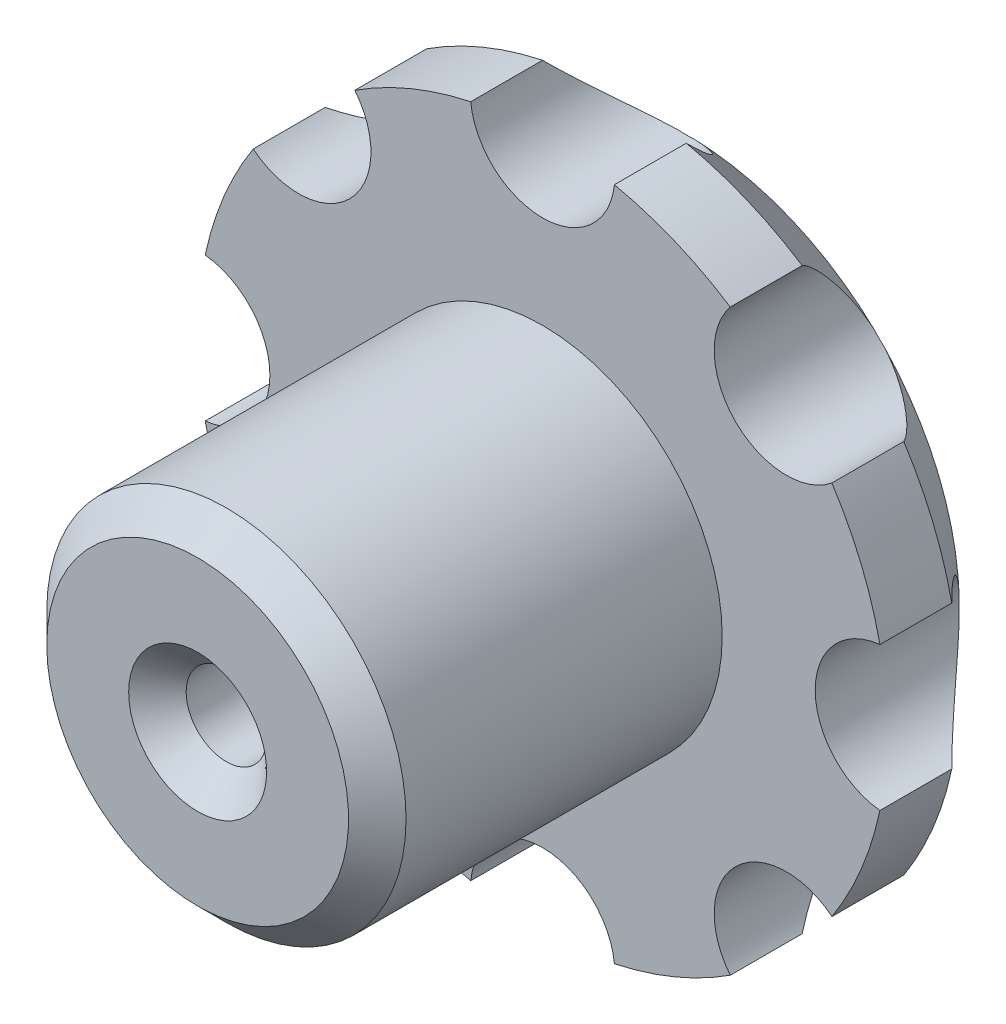
SolidWorks part; units mm, degrees
material "S235JR"
ref_plane "xy" through (0, 0, 0) normal (0, 0, 1) x (1, 0, 0)
ref_plane "xz" through (0, 0, 0) normal (0, 1, 0) x (1, 0, 0)
ref_plane "yz" through (0, 0, 0) normal (1, 0, 0) x (0, 0, -1)
ref_axis "x" through (-88.99, 0, 0) along (1, 0, 0)
ref_axis "y" through (0, 55, 0) along (0, -1, 0)
ref_axis "z" through (0, 0, -88.99) along (0, 0, 1)
sketch "Skizze1" plane through (0, 0, 0) normal (0, 1, 0) x (1, 0, 0)
  line L0 (0, 0) -> (-19, 0)
  line L1 (-19, 0) -> (-24, -5)
  line L2 (-24, -5) -> (-24, -10)
  line L3 (-24, -10) -> (-12.5, -10)
  line L4 (-12.5, -10) -> (-12.5, -34)
  line L5 (-12.5, -34) -> (0, -34)
  line L6 (0, -34) -> (0, 0)
  dimension "D1" = 12.5
  dimension "D2" = 24
  dimension "D3" = 24
  dimension "D4" = 45
  dimension "D5" = 5
  dimension "D6" = 10
revolve "Rotation1" add sketch "Skizze1" angle 360 about L6
sketch "Skizze2" plane through (0, 0, 0) normal (0, 0, 1) x (1, 0, 0)
  arc A0 (-5, 23.4734) -> (5, 23.4734) centre (0, 24) ccw
  arc A1 (-5, 23.4734) -> (5, 23.4734) centre (0, 0) cw
  circle A2 centre (0, 0) radius 24 construction
  dimension "D1" = 10
extrude "Schnitt-Linear austragen1" cut sketch "Skizze2" along normal through all
pattern_circular "Kreismuster1" count 8 over 360 about axis through (0, 0, -88.99) along (0, 0, 1) of "Schnitt-Linear austragen1"
sketch "Skizze3" plane through (0, 0, 0) normal (0, 1, 0) x (1, 0, 0)
  line L0 (0, 0) -> (0, -2.5)
  line L1 (0, -2.5) -> (-2.5, 0)
  line L2 (-2.5, 0) -> (0, 0)
  line L4 (0, -4.5) -> (-2.8, -4.5)
  line L5 (0, -4.5) -> (0, -34)
  line L6 (0, -34) -> (-2.8, -34)
  line L7 (-2.8, -4.5) -> (-2.8, -34)
  dimension "D1" = 45
  dimension "D2" = 2.5
  dimension "D3" = 2
  dimension "D4" = 2.8
revolve "Schnitt-Rotation1" cut sketch "Skizze3" angle 360 about L0
chamfer "Fase1" distance 2 angle 45 2 edges at (12.5, 0, 34) (-2.8, 0, 34)
